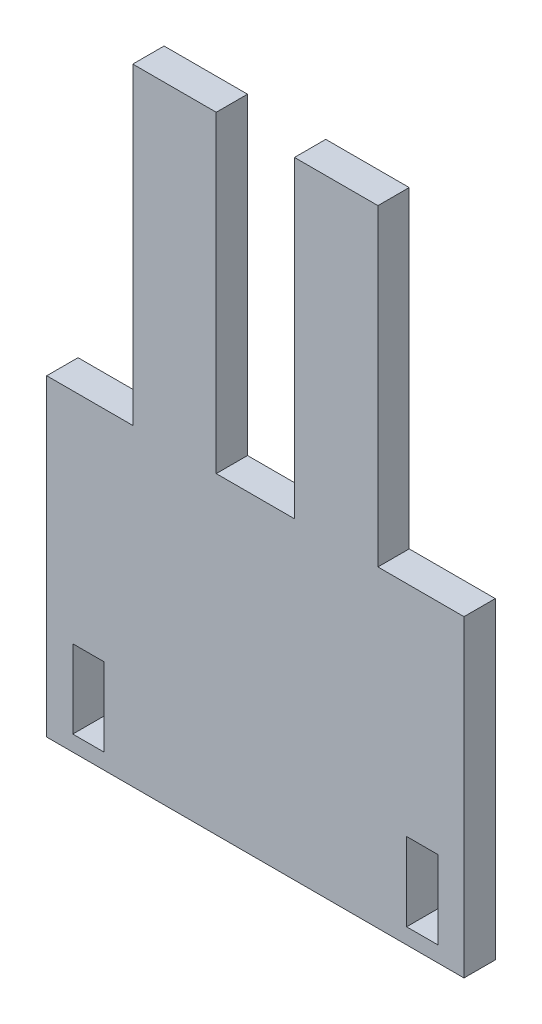
SolidWorks part; units mm, degrees
ref_plane "Plan de face" through (0, 0, 0) normal (0, 0, 1) x (1, 0, 0)
ref_plane "Plan de dessus" through (0, 0, 0) normal (0, 1, 0) x (1, 0, 0)
ref_plane "Plan de droite" through (0, 0, 0) normal (1, 0, 0) x (0, 0, -1)
sketch "Esquisse1" plane through (0, 0, 0) normal (0, 0, 1) x (1, 0, 0)
  line L0 (23.0676, -72.6187) -> (23.0676, -12.6187)
  line L1 (23.0676, -12.6187) -> (6.5676, -12.6187)
  line L2 (6.5676, -12.6187) -> (6.5676, 47.3813)
  line L3 (-56.9324, -72.6187) -> (23.0676, -72.6187)
  line L4 (6.5676, 47.3813) -> (-9.4324, 47.3813)
  line L5 (18.0676, -54.6187) -> (12.0676, -54.6187)
  line L6 (18.0676, -54.6187) -> (18.0676, -69.6187)
  line L7 (18.0676, -69.6187) -> (12.0676, -69.6187)
  line L8 (12.0676, -54.6187) -> (12.0676, -69.6187)
  line L9 (-45.9324, -54.6187) -> (-51.9324, -54.6187)
  line L10 (-45.9324, -54.6187) -> (-45.9324, -69.6187)
  line L11 (-45.9324, -69.6187) -> (-51.9324, -69.6187)
  line L12 (-51.9324, -54.6187) -> (-51.9324, -69.6187)
  line L13 (-9.4324, 47.3813) -> (-9.4324, -12.6187)
  line L14 (-9.4324, -12.6187) -> (-24.4324, -12.6187)
  line L15 (-24.4324, -12.6187) -> (-24.4324, 47.3813)
  line L16 (-24.4324, 47.3813) -> (-40.4324, 47.3813)
  line L17 (-40.4324, 47.3813) -> (-40.4324, -12.6187)
  line L18 (-40.4324, -12.6187) -> (-56.9324, -12.6187)
  line L19 (-56.9324, -12.6187) -> (-56.9324, -72.6187)
  dimension "D2" = 120
  dimension "D3" = 6
  dimension "D4" = 15
  dimension "D5" = 6
  dimension "D6" = 15
  dimension "D7" = 80
  dimension "D8" = 16.5
  dimension "D9" = 3
  dimension "D10" = 3
  dimension "D11" = 16
  dimension "D12" = 16.5
  dimension "D13" = 16
  dimension "D14" = 15
  dimension "D15" = 60
  dimension "D16" = 60
  dimension "D17" = 60
  dimension "D18" = 60
  dimension "D19" = 5
  dimension "D20" = 5
extrude "Boss.-Extru.1" add sketch "Esquisse1" along normal blind 6
